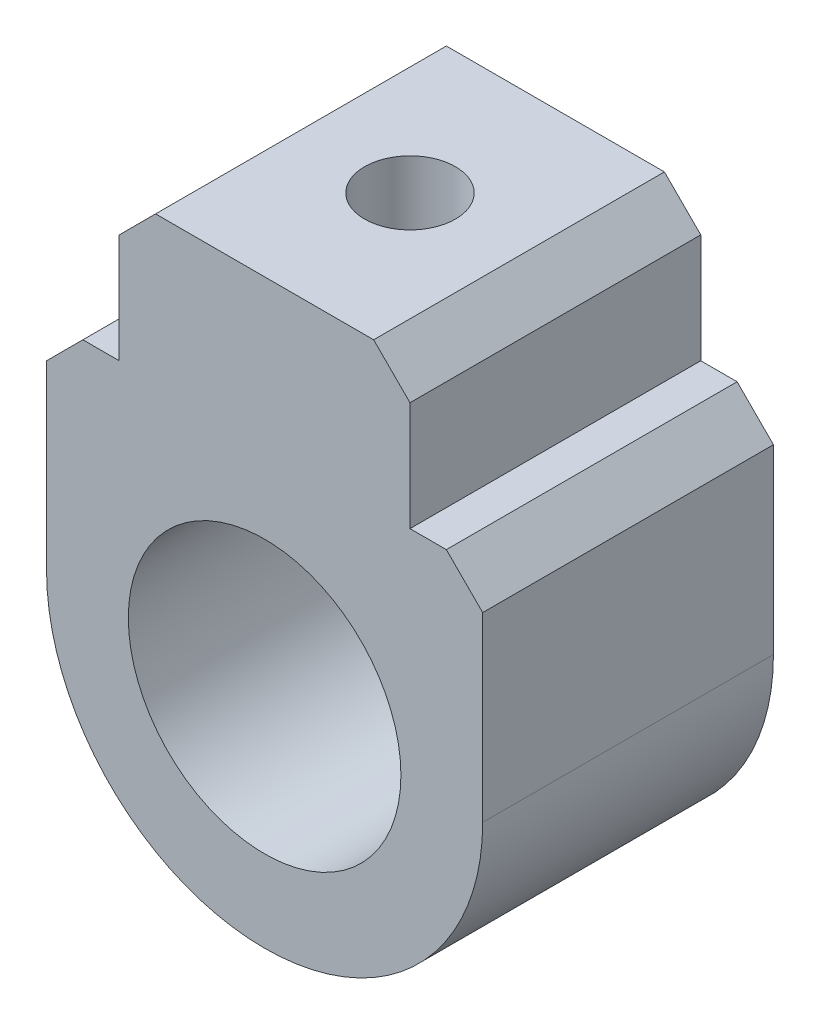
SolidWorks part; units mm, degrees
material "PTFE (general)"
ref_plane "Front Plane" through (0, 0, 0) normal (0, 0, 1) x (1, 0, 0)
ref_plane "Top Plane" through (0, 0, 0) normal (0, 1, 0) x (1, 0, 0)
ref_plane "Right Plane" through (0, 0, 0) normal (1, 0, 0) x (0, 0, -1)
sketch "Sketch1" plane through (0, 0, 0) normal (0, 0, 1) x (1, 0, 0)
  line L2 (-6, 0) -> (-6, 6)
  line L3 (-6, 6) -> (-4, 6)
  line L4 (6, 0) -> (6, 6)
  line L7 (-4, 6) -> (-4, 10)
  line L8 (-4, 10) -> (4, 10)
  line L10 (4, 10) -> (4, 6)
  line L12 (4, 6) -> (6, 6)
  arc A0 (-6, 0) -> (6, 0) centre (0, 0) ccw
  circle A5 centre (0, 0) radius 3.75
  point P7 (-0.3536, -0.3536)
  point P13 (4.057, -4.7641)
  point P14 (0.25, 0.433)
  point P15 (5.4462, -2.567)
  point P20 (-0.3536, -0.3536)
  point P22 (-0.3536, 0.3536)
  point P29 (-4.5962, -3.8891)
  point P30 (0.3536, -0.3536)
  point P31 (-3.8891, -4.5962)
  point P32 (-0.3536, -0.3536)
  point P33 (-4.5962, 3.8891)
  point P34 (0.3536, 0.3536)
  point P35 (-3.8891, 4.5962)
  point P36 (-0.3536, 0.3536)
  point P37 (3.8891, 4.5962)
  point P39 (4.5962, 3.8891)
  dimension "D1" = 6
  dimension "D6" = 7.5
  dimension "D2" = 6
  dimension "D3" = 4
  dimension "D8" = 8
  dimension "D13" = 4
  dimension "D17" = 6
extrude "Boss-Extrude2" add sketch "Sketch1" along normal blind 8
ref_axis "Axis1" through (0, 0, 8) along (0, 0, -1)
ref_plane "Plane1" through (0, 0, 0) normal (0, 1, 0) x (-1, 0, 0)
sketch "Sketch11" plane through (0, 10, 0) normal (0, 1, 0) x (1, 0, 0)
  line L0 (0, -8) -> (0, 0) construction
  line L1 (4, -8) -> (-4, -8) construction
  circle A0 centre (0, -4) radius 1.25
  dimension "D1" = 2.5
  dimension "D2" = 4
extrude "Cut-Extrude5" cut sketch "Sketch11" against normal blind 5
chamfer "Chamfer1" distance 1 angle 45 4 edges at (-6, 6, 4) (6, 6, 4) (-4, 10, 4) (4, 10, 4)
